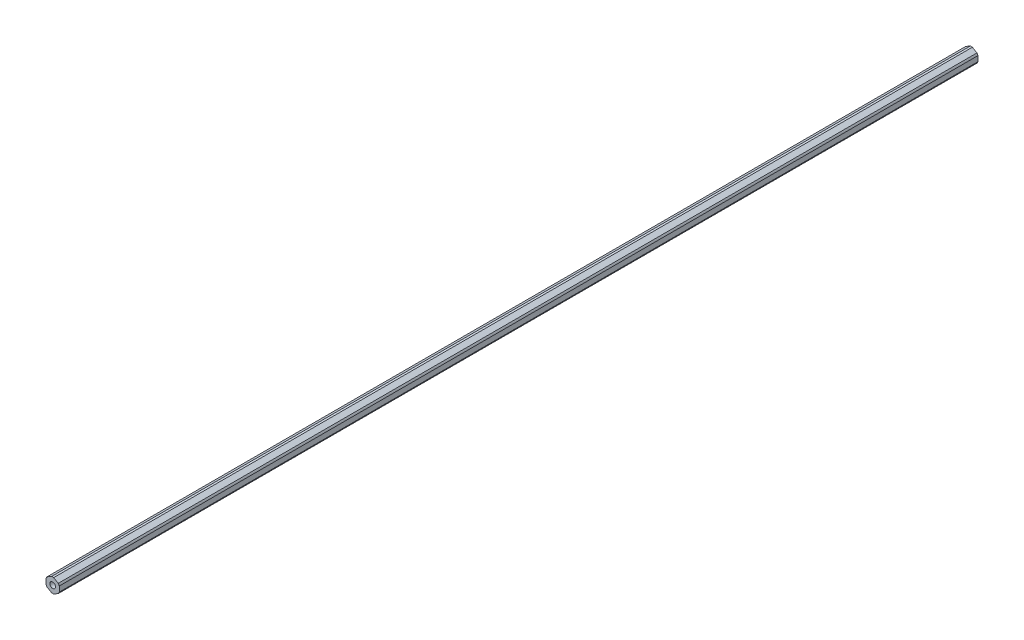
SolidWorks part; units mm, degrees
material "7075-T6 (SN)"
ref_plane "Front Plane" through (0, 0, 0) normal (0, 0, 1) x (1, 0, 0)
ref_plane "Top Plane" through (0, 0, 0) normal (0, 1, 0) x (1, 0, 0)
ref_plane "Right Plane" through (0, 0, 0) normal (1, 0, 0) x (0, 0, -1)
sketch "Sketch2" plane through (0, 0, 0) normal (0, 0, 1) x (1, 0, 0)
  line L1 (0, 5.4993) -> (-4.7625, 2.7496)
  line L2 (-4.7625, 2.7496) -> (-4.7625, -2.7496)
  line L3 (-4.7625, -2.7496) -> (0, -5.4993)
  line L4 (0, -5.4993) -> (4.7625, -2.7496)
  line L5 (4.7625, -2.7496) -> (4.7625, 2.7496)
  line L6 (4.7625, 2.7496) -> (0, 5.4993)
  circle A0 centre (0, 0) radius 4.7625 construction
  circle A2 centre (0, 0) radius 2.0193
  circle A3 centre (0, 0) radius 5.125
  dimension "D1" = 9.525
  dimension "D2" = 10.25
  dimension "D3" = 4.0386
extrude "Boss-Extrude1" add sketch "Sketch2" along normal mid plane 657.7302 contours L5 A3 L6 L1 L2 L3 L4 A2 region at (0, 4.9851, 0)
hole_wizard "#10-32 Tapped Hole2" positions "3DSketch1" profile "Sketch6" tap size "#10-32" standard "ANSI Inch"
sketch3d "3DSketch1"
  circle A0 centre (0, 0, 328.8651) radius 2.0193 construction
  circle A1 centre (0, 0, -328.8651) radius 2.0193 construction
  point P0 (0, 0, -328.8651)
  point P2 (0, 0, 328.8651)
  point P7 (0, 0, 330.8844)
  point P10 (0, 0, -326.8458)
sketch "Sketch6" plane through (0, 0, -328.8651) normal (1, 0, 0) x (0, 1, 0)
  line L0 (0, 0) -> (0, 17.5608)
  line L1 (0, 17.5608) -> (2.0193, 16.3474)
  line L2 (2.0193, 16.3474) -> (2.0193, 0)
  line L5 (2.0193, 0) -> (0, 0)
  line L10 (0, 17.5608) -> (-2.0193, 16.3474) construction
  line L11 (0, -6.35) -> (0, 107.95) construction
  dimension "Tap Drill Dia." = 4.0386
  dimension "Tap Drill Depth" = 16.3474
  dimension "Drill Angle" = 118
cosmetic thread "Hole Thread2"
cosmetic thread "Hole Thread3"
equation "\"D2@Sketch2\"=10.25mm"
